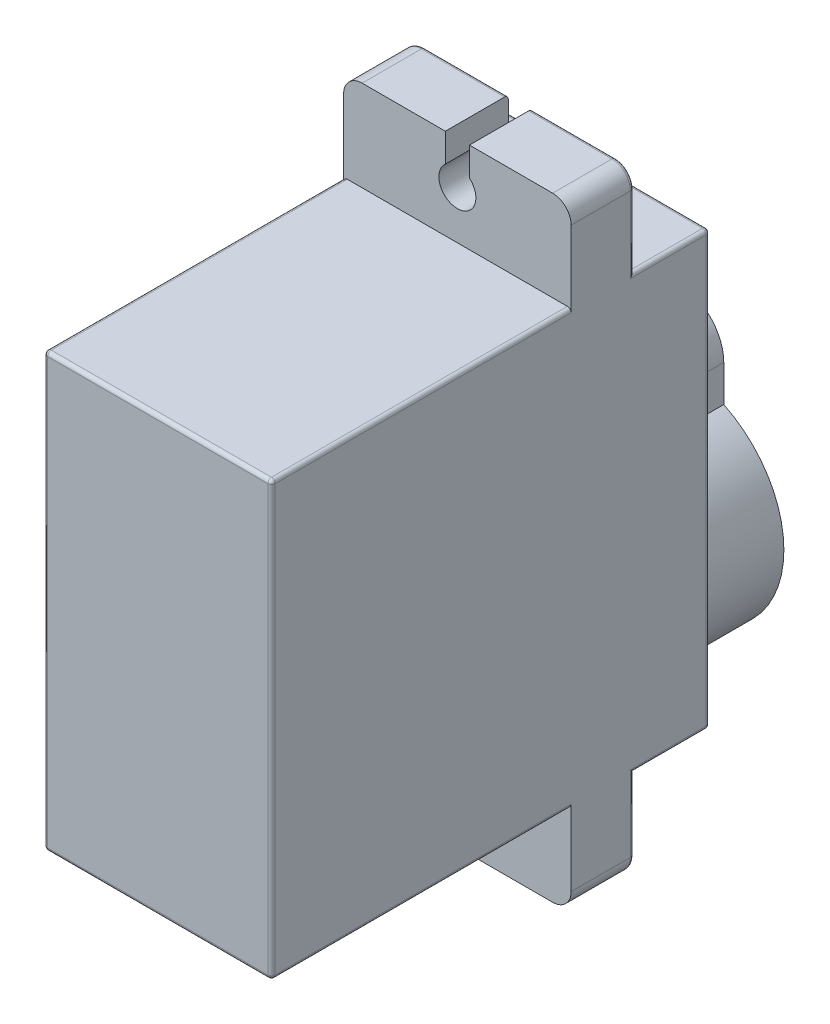
SolidWorks part; units mm, degrees
ref_plane "Płaszczyzna przednia" through (0, 0, 0) normal (0, 0, 1) x (1, 0, 0)
ref_plane "Płaszczyzna górna" through (0, 0, 0) normal (0, 1, 0) x (1, 0, 0)
ref_plane "Płaszczyzna prawa" through (0, 0, 0) normal (1, 0, 0) x (0, 0, -1)
sketch "Szkic1" plane through (0, 0, 0) normal (1, 0, 0) x (0, 0, -1)
  line L0 (0, 0) -> (0, 23.4)
  line L1 (0, 23.4) -> (16.2, 23.4)
  line L2 (16.2, 23.4) -> (16.2, 28.3)
  line L3 (16.2, 28.3) -> (19.6, 28.3)
  line L4 (19.6, 28.3) -> (19.6, 23.4)
  line L5 (19.6, 23.4) -> (23.7, 23.4)
  line L6 (23.7, 23.4) -> (23.7, 0)
  line L7 (23.7, 0) -> (19.6, 0)
  line L8 (19.6, 0) -> (19.6, -4.9)
  line L9 (19.6, -4.9) -> (16.2, -4.9)
  line L10 (16.2, -4.9) -> (16.2, 0)
  line L11 (16.2, 0) -> (0, 0)
  dimension "D1" = 23.7
  dimension "D2" = 4.1
  dimension "D3" = 3.4
  dimension "D4" = 23.4
  dimension "D6" = 4.9
extrude "Dodanie-wyciągnięcie1" add sketch "Szkic1" along normal blind 12.3
fillet "Zaokrąglenie1" radius 0.2 22 edges at (6.15, 23.4, 0) (0, 11.7, 0) (12.3, 11.7, 0) (6.15, 0, 0) (0, 0, -8.1) (0, 0, -21.65) (0, -2.45, -19.6) (6.15, -4.9, -19.6) (12.3, 0, -21.65) (12.3, -2.45, -19.6) (12.3, 0, -8.1) (0, 25.85, -19.6) (12.3, 25.85, -19.6) (6.15, 28.3, -19.6) (6.15, 0, -23.7) (0, 11.7, -23.7) (12.3, 11.7, -23.7) (6.15, 23.4, -23.7) (0, 23.4, -8.1) (0, 23.4, -21.65) (12.3, 23.4, -8.1) (12.3, 23.4, -21.65)
fillet "Zaokrąglenie2" radius 1 8 edges at (12.2414, -4.8414, -19.5414) (0.0586, -4.8414, -19.5414) (0.0586, 28.2414, -19.5414) (12.2414, 28.2414, -19.5414) (12.3, 28.3, -17.8) (0, 28.3, -17.8) (0, -4.9, -17.8) (12.3, -4.9, -17.8)
sketch "Szkic2" plane through (0, 0, -23.7) normal (0, 0, -1) x (-1, 0, 0)
  line L0 (-0.2, 0.2) -> (-12.1, 0.2) construction
  line L1 (-3.65, 13.1) -> (-3.65, 11.1281)
  line L2 (-8.65, 13.1) -> (-8.65, 11.1281)
  arc A0 (-8.65, 11.1281) -> (-3.65, 11.1281) centre (-6.15, 5.95) ccw
  arc A1 (-3.65, 13.1) -> (-8.65, 13.1) centre (-6.15, 13.1) ccw
  point P7 (-6.15, 0.2)
  dimension "D1" = 11.5
  dimension "D2" = 5
  dimension "D3" = 12.9
extrude "Dodanie-wyciągnięcie2" add sketch "Szkic2" along normal blind 4.4
sketch "Szkic3" plane through (0, 0, -28.1) normal (0, 0, -1) x (-1, 0, 0)
  circle A0 centre (-6.15, 5.95) radius 2.45
  dimension "D1" = 4.9
extrude "Wytnij-wyciągnięcie1" cut sketch "Szkic3" against normal blind 3.2
sketch "Szkic4" plane through (0, 0, -28.1) normal (0, 0, -1) x (-1, 0, 0)
  line L0 (-6.15, 5.95) -> (-23.9, 5.95) construction
  dimension "D1" = 17.75
sketch "Szkic5" plane through (0, 0, -19.6) normal (0, 0, -1) x (-1, 0, 0)
  line L0 (-12.1, 23.4) -> (-0.2, 23.4) construction
  line L1 (-5.5, 26.7599) -> (-5.5, 28.3)
  line L2 (-11.3, 28.3) -> (-1, 28.3) construction
  line L3 (-5.5, 28.3) -> (-6.8, 28.3)
  line L4 (-6.8, 28.3) -> (-6.8, 26.7599)
  line L5 (-6.15, 28.3) -> (-6.15, 27.4) construction
  arc A0 (-6.8, 26.7599) -> (-5.5, 26.7599) centre (-6.15, 26) ccw
  point P2 (-6.15, 25)
  point P3 (-6.15, 23.4)
  dimension "D1" = 2
  dimension "D2" = 2.3
  dimension "D3" = 1.3
extrude "Wytnij-wyciągnięcie2" cut sketch "Szkic5" against normal up to next
ref_plane "Płaszczyzna1" through (0, 11.7, 0) normal (0, 1, 0) x (1, 0, 0)
mirror "Lustro1" about plane through (0, 11.7, 0) normal (0, 1, 0) of "Wytnij-wyciągnięcie2"
